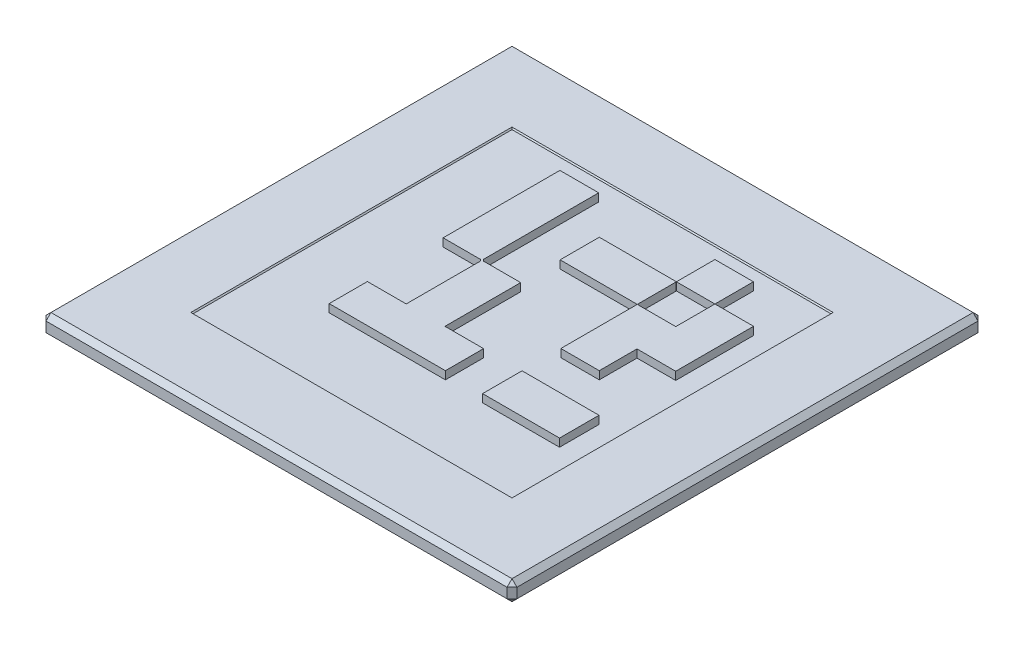
SolidWorks part; units mm, degrees
other "Title Block Table1"
other "DetailItem1"
ref_plane "Front Plane" through (0, 0, 0) normal (0, 0, 1) x (1, 0, 0)
ref_plane "Top Plane" through (0, 0, 0) normal (0, 1, 0) x (1, 0, 0)
ref_plane "Right Plane" through (0, 0, 0) normal (1, 0, 0) x (0, 0, -1)
sketch "ss" plane through (0, 0, 0) normal (0, 1, 0) x (1, 0, 0)
  line L4 (74.93, 0) -> (74.93, 74.93)
  line L5 (0, 74.93) -> (74.93, 74.93)
  line L6 (0, 0) -> (0, 74.93)
  line L7 (0, 0) -> (74.93, 0)
  line L8 (0, 74.93) -> (74.93, 0) construction
  line L9 (74.93, 74.93) -> (0, 0) construction
  point P4 (37.465, 37.465)
  dimension "D1" = 74.93
extrude "Boss-Extrude2" add sketch "ss" along normal blind 3.175 separate body
sketch "Sketch2" plane through (0, 0, 0) normal (0, 1, 0) x (1, 0, 0)
  line L0 (91.5, 270) -> (457.5, 270) construction
  line L1 (22.7893, 59.7597) -> (28.965, 59.7597)
  line L2 (28.965, 59.7597) -> (28.965, 41.4275)
  line L3 (29.1708, 41.1823) -> (35.1306, 41.1823)
  line L4 (35.1306, 41.1823) -> (35.1306, 29.1337)
  line L5 (35.1306, 29.1337) -> (41.275, 29.1337)
  line L6 (41.275, 29.1337) -> (41.275, 23.0583)
  line L7 (41.275, 23.0583) -> (22.7893, 23.0583)
  line L8 (22.7893, 23.0583) -> (22.7893, 29.1337)
  line L9 (22.7893, 29.1337) -> (28.965, 29.1337)
  line L10 (28.965, 29.1337) -> (28.965, 40.9602)
  line L11 (28.7787, 41.1823) -> (22.7893, 41.1823)
  line L12 (22.7893, 41.1823) -> (22.7893, 59.7597)
  line L13 (47.4041, 59.8127) -> (53.5307, 59.8127)
  line L14 (53.5307, 59.8127) -> (53.5307, 53.7193)
  line L15 (53.5637, 53.6862) -> (59.6767, 53.6862)
  line L16 (59.6767, 53.6862) -> (59.6767, 41.2982)
  line L17 (59.6767, 41.2982) -> (53.5164, 41.2982)
  line L18 (53.5164, 41.2982) -> (53.5164, 35.2984)
  line L19 (53.5164, 35.2984) -> (47.4041, 35.2984)
  line L20 (47.4041, 35.2984) -> (47.4041, 47.4401)
  line L21 (47.3899, 47.4543) -> (35.1306, 47.4543)
  line L22 (35.1306, 47.4543) -> (35.1306, 53.6862)
  line L23 (35.1306, 53.6862) -> (47.3752, 53.6862)
  line L24 (47.4041, 53.7152) -> (47.4041, 59.8127)
  line L25 (59.6393, 29.1337) -> (59.6393, 22.8517)
  line L26 (59.6393, 22.8517) -> (47.3949, 22.8517)
  line L27 (47.3949, 22.8517) -> (47.3949, 29.1337)
  line L28 (47.3949, 29.1337) -> (59.6393, 29.1337)
  line L29 (47.4184, 47.4543) -> (53.5307, 47.4543)
  line L30 (53.5307, 47.4543) -> (53.5307, 53.6531)
  line L31 (47.4041, 53.6356) -> (47.4041, 47.4685)
  line L32 (53.4976, 53.6862) -> (47.4547, 53.6862)
  line L33 (47.3899, 47.4543) -> (47.4041, 47.4401)
  line L34 (16.7542, 16.3992) -> (65.7958, 16.3992)
  line L35 (16.7542, 16.3992) -> (16.7542, 65.9653)
  line L36 (16.7542, 65.9653) -> (65.7958, 65.9653)
  line L37 (65.7958, 16.3992) -> (65.7958, 65.9653)
  line L38 (16.7542, 16.3992) -> (65.7958, 65.9653) construction
  line L39 (16.7542, 65.9653) -> (65.7958, 16.3992) construction
  line L40 (4.5032, 4.4545) -> (78.0468, 4.4545)
  line L41 (4.5032, 4.4545) -> (4.5032, 77.9101)
  line L42 (4.5032, 77.9101) -> (78.0468, 77.9101)
  line L43 (78.0468, 4.4545) -> (78.0468, 77.9101)
  line L44 (4.5032, 4.4545) -> (78.0468, 77.9101) construction
  line L45 (4.5032, 77.9101) -> (78.0468, 4.4545) construction
  line L46 (47.4041, 47.4685) -> (47.4184, 47.4543)
  line L47 (53.5307, 53.7193) -> (53.5637, 53.6862)
  line L48 (53.4976, 53.6862) -> (53.5307, 53.6531)
  line L49 (47.4041, 53.7152) -> (47.3752, 53.6862)
  line L50 (47.4547, 53.6862) -> (47.4041, 53.6356)
  line L51 (28.7787, 41.1823) -> (28.965, 40.9602)
  line L52 (28.965, 41.4275) -> (29.1708, 41.1823)
  line L53 (74.93, 0) -> (74.93, 74.93) construction
  line L54 (0, 74.93) -> (0, 0) construction
  point P30 (41.275, 41.1823)
  point P36 (41.275, 41.1823)
  dimension "D1" = 3.1168
  dimension "D2" = 4.5032
sketch "Sketch5" plane through (0, 3.175, 0) normal (0, 1, 0) x (1, 0, 0)
  line L0 (12.7, 12.7) -> (62.23, 12.7)
  line L1 (62.23, 12.7) -> (62.23, 62.23)
  line L2 (62.23, 62.23) -> (12.7, 62.23)
  line L3 (12.7, 62.23) -> (12.7, 12.7)
  line L8 (0, 0) -> (74.93, 0)
  line L9 (74.93, 0) -> (74.93, 74.93)
  line L10 (74.93, 74.93) -> (0, 74.93)
  line L11 (0, 74.93) -> (0, 0)
  line L12 (0, 0) -> (74.93, 0)
  line L13 (74.93, 0) -> (74.93, 74.93)
  line L14 (74.93, 74.93) -> (0, 74.93)
  line L15 (0, 74.93) -> (0, 0)
  dimension "D1" = 0
  dimension "D2" = 12.7
extrude "Cut-Extrude1" cut sketch "Sketch5" against normal blind 0.1778 contours L2 L3 L0 L1 region at (37.465, 3.175, -37.465)
sketch "Sketch10" plane through (0, 3.175, 0) normal (0, 1, 0) x (1, 0, 0)
  line L0 (75.565, 37.465) -> (74.93, 37.465) construction
  line L1 (-0.635, 75.565) -> (75.565, 75.565)
  line L2 (-0.635, 75.565) -> (-0.635, -0.635)
  line L3 (-0.635, -0.635) -> (75.565, -0.635)
  line L4 (75.565, 75.565) -> (75.565, -0.635)
  line L5 (-0.635, 75.565) -> (75.565, -0.635) construction
  line L6 (-0.635, -0.635) -> (75.565, 75.565) construction
  line L7 (74.93, 0) -> (74.93, 74.93) construction
  line L8 (37.465, -0.635) -> (37.465, 0) construction
  line L9 (0, 0) -> (74.93, 0) construction
  point P0 (37.465, 37.465)
  dimension "D1" = 76.2
  dimension "D2" = 76.2
chamfer "Chamfer1" distance 0.7874 angle 45 16 edges at (37.465, 3.175, -74.93) (74.93, 3.175, -37.465) (37.465, 3.175, 0) (0, 3.175, -37.465) (37.465, 0, -74.93) (74.93, 1.5875, -74.93) (74.93, 0, -37.465) (0, 1.5875, -74.93) (0, 0, -37.465) (0, 1.5875, 0) (74.93, 1.5875, 0) (37.465, 0, 0) (12.7, 3.175, -37.465) (37.465, 3.175, -12.7) (62.23, 3.175, -37.465) (37.465, 3.175, -62.23)
sketch "Sketch7" plane through (0, 0, 0) normal (0, -1, 0) x (1, 0, 0)
  line L0 (3.4345, -26.528) -> (75.4032, -26.528) construction
  text T0 "GLOBAL MARKER\r\nIF LOST RETURN TO \r\nMAX DE ARRIZ\r\nEX: 1323" font "Century Gothic" height in points 20
extrude "Cut-Extrude2" cut sketch "Sketch7" against normal blind 0.381
sketch "Esquisse1" plane through (0, 2.9972, 0) normal (0, 1, 0) x (1, 0, 0)
  line L4 (59.6393, 22.8517) -> (59.6393, 29.1337)
  line L5 (47.3949, 22.8517) -> (59.6393, 22.8517)
  line L6 (47.3949, 29.1337) -> (47.3949, 22.8517)
  line L7 (59.6393, 29.1337) -> (47.3949, 29.1337)
  line L8 (59.6393, 22.8517) -> (59.6393, 29.1337)
  line L9 (47.3949, 22.8517) -> (59.6393, 22.8517)
  line L10 (47.3949, 29.1337) -> (47.3949, 22.8517)
  line L11 (59.6393, 29.1337) -> (47.3949, 29.1337)
  line L12 (4.5032, 4.4545) -> (78.0468, 4.4545)
  line L13 (78.0468, 4.4545) -> (78.0468, 77.9101)
  line L14 (78.0468, 77.9101) -> (4.5032, 77.9101)
  line L15 (4.5032, 77.9101) -> (4.5032, 4.4545)
  line L16 (4.5032, 4.4545) -> (78.0468, 4.4545)
  line L17 (78.0468, 4.4545) -> (78.0468, 77.9101)
  line L18 (78.0468, 77.9101) -> (4.5032, 77.9101)
  line L19 (4.5032, 77.9101) -> (4.5032, 4.4545)
  line L20 (16.7542, 16.3992) -> (65.7958, 16.3992)
  line L21 (65.7958, 16.3992) -> (65.7958, 65.9653)
  line L22 (65.7958, 65.9653) -> (16.7542, 65.9653)
  line L23 (16.7542, 65.9653) -> (16.7542, 16.3992)
  line L24 (16.7542, 16.3992) -> (65.7958, 16.3992)
  line L25 (65.7958, 16.3992) -> (65.7958, 65.9653)
  line L26 (65.7958, 65.9653) -> (16.7542, 65.9653)
  line L27 (16.7542, 65.9653) -> (16.7542, 16.3992)
  line L31 (47.4041, 53.6356) -> (47.4041, 47.4685)
  line L32 (47.4041, 47.4685) -> (47.4184, 47.4543)
  line L33 (47.4184, 47.4543) -> (53.5307, 47.4543)
  line L34 (53.5307, 47.4543) -> (53.5307, 53.6531)
  line L35 (53.5307, 53.6531) -> (53.4976, 53.6862)
  line L36 (53.4976, 53.6862) -> (47.4547, 53.6862)
  line L37 (47.4547, 53.6862) -> (47.4041, 53.6356)
  line L38 (47.4041, 53.6356) -> (47.4041, 47.4685)
  line L39 (47.4041, 47.4685) -> (47.4184, 47.4543)
  line L40 (47.4184, 47.4543) -> (53.5307, 47.4543)
  line L41 (53.5307, 47.4543) -> (53.5307, 53.6531)
  line L42 (53.5307, 53.6531) -> (53.4976, 53.6862)
  line L43 (53.4976, 53.6862) -> (47.4547, 53.6862)
  line L44 (47.4547, 53.6862) -> (47.4041, 53.6356)
  line L52 (35.1306, 41.1823) -> (29.1708, 41.1823)
  line L53 (47.3752, 53.6862) -> (35.1306, 53.6862)
  line L54 (35.1306, 53.6862) -> (35.1306, 47.4543)
  line L55 (35.1306, 47.4543) -> (47.3899, 47.4543)
  line L56 (47.3899, 47.4543) -> (47.4041, 47.4401)
  line L57 (47.4041, 47.4401) -> (47.4041, 35.2984)
  line L58 (47.4041, 35.2984) -> (53.5164, 35.2984)
  line L59 (53.5164, 35.2984) -> (53.5164, 41.2982)
  line L60 (53.5164, 41.2982) -> (59.6767, 41.2982)
  line L61 (59.6767, 41.2982) -> (59.6767, 53.6862)
  line L62 (59.6767, 53.6862) -> (53.5637, 53.6862)
  line L63 (53.5637, 53.6862) -> (53.5307, 53.7193)
  line L64 (53.5307, 53.7193) -> (53.5307, 59.8127)
  line L65 (53.5307, 59.8127) -> (47.4041, 59.8127)
  line L66 (47.4041, 59.8127) -> (47.4041, 53.7152)
  line L67 (47.4041, 53.7152) -> (47.3752, 53.6862)
  line L68 (47.3752, 53.6862) -> (35.1306, 53.6862)
  line L69 (35.1306, 53.6862) -> (35.1306, 47.4543)
  line L70 (35.1306, 47.4543) -> (47.3899, 47.4543)
  line L71 (47.3899, 47.4543) -> (47.4041, 47.4401)
  line L72 (47.4041, 47.4401) -> (47.4041, 35.2984)
  line L73 (47.4041, 35.2984) -> (53.5164, 35.2984)
  line L74 (53.5164, 35.2984) -> (53.5164, 41.2982)
  line L75 (53.5164, 41.2982) -> (59.6767, 41.2982)
  line L76 (59.6767, 41.2982) -> (59.6767, 53.6862)
  line L77 (59.6767, 53.6862) -> (53.5637, 53.6862)
  line L78 (53.5637, 53.6862) -> (53.5307, 53.7193)
  line L79 (53.5307, 53.7193) -> (53.5307, 59.8127)
  line L80 (53.5307, 59.8127) -> (47.4041, 59.8127)
  line L81 (47.4041, 59.8127) -> (47.4041, 53.7152)
  line L82 (47.4041, 53.7152) -> (47.3752, 53.6862)
  line L83 (35.1306, 29.1337) -> (35.1306, 41.1823)
  line L84 (41.275, 29.1337) -> (35.1306, 29.1337)
  line L85 (41.275, 23.0583) -> (41.275, 29.1337)
  line L86 (22.7893, 23.0583) -> (41.275, 23.0583)
  line L87 (22.7893, 29.1337) -> (22.7893, 23.0583)
  line L88 (28.965, 29.1337) -> (22.7893, 29.1337)
  line L89 (28.965, 40.9602) -> (28.965, 29.1337)
  line L90 (28.7787, 41.1823) -> (28.965, 40.9602)
  line L91 (22.7893, 41.1823) -> (28.7787, 41.1823)
  line L92 (22.7893, 59.7597) -> (22.7893, 41.1823)
  line L93 (28.965, 59.7597) -> (22.7893, 59.7597)
  line L94 (28.965, 41.4275) -> (28.965, 59.7597)
  line L95 (29.1708, 41.1823) -> (28.965, 41.4275)
  line L96 (35.1306, 41.1823) -> (29.1708, 41.1823)
  line L97 (35.1306, 29.1337) -> (35.1306, 41.1823)
  line L98 (41.275, 29.1337) -> (35.1306, 29.1337)
  line L99 (41.275, 23.0583) -> (41.275, 29.1337)
  line L100 (22.7893, 23.0583) -> (41.275, 23.0583)
  line L101 (22.7893, 29.1337) -> (22.7893, 23.0583)
  line L102 (28.965, 29.1337) -> (22.7893, 29.1337)
  line L103 (28.965, 40.9602) -> (28.965, 29.1337)
  line L104 (28.7787, 41.1823) -> (28.965, 40.9602)
  line L105 (22.7893, 41.1823) -> (28.7787, 41.1823)
  line L106 (22.7893, 59.7597) -> (22.7893, 41.1823)
  line L107 (28.965, 59.7597) -> (22.7893, 59.7597)
  line L108 (28.965, 41.4275) -> (28.965, 59.7597)
  line L109 (29.1708, 41.1823) -> (28.965, 41.4275)
  dimension "D1" = 0
  dimension "D2" = 0
  dimension "D3" = 0
  dimension "D4" = 0
  dimension "D5" = 0
  dimension "D6" = 0
extrude "Boss.-Extru.1" add sketch "Esquisse1" along normal blind 1.27 contours L96 L109 L108 L107 L106 L105 L104 L103 L102 L101 L100 L99 L98 L97 | L81 L82 L68 L69 L70 L71 L72 L73 L74 L75 L76 L77 L78 L79 L80 L44 L43 L42 L41 L40 L39 L38 | L8 L11 L10 L9 region at (53.5171, 2.9972, -25.9927) region at (29.6924, 2.9972, -37.6115) region at (47.4142, 2.9972, -53.6762)
